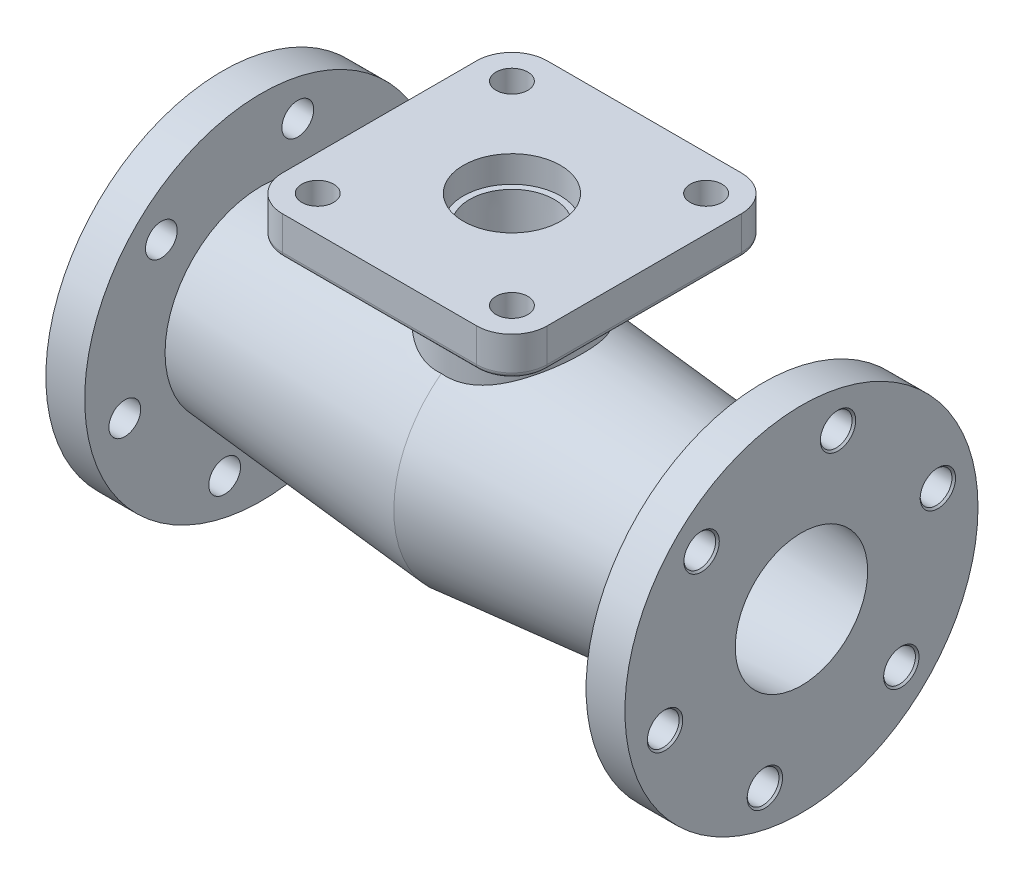
SolidWorks part; units mm, degrees
ref_plane "Front Plane" through (0, 0, 0) normal (0, 0, 1) x (1, 0, 0)
ref_plane "Top Plane" through (0, 0, 0) normal (0, 1, 0) x (1, 0, 0)
ref_plane "Right Plane" through (0, 0, 0) normal (1, 0, 0) x (0, 0, -1)
sketch "Sketch1" plane through (0, 0, 0) normal (0, 0, 1) x (1, 0, 0)
  line L0 (0, 0) -> (0, 98620.7422) construction
  line L1 (0, 0) -> (-98620.7422, 0) construction
  line L2 (0, -51.8481) -> (-164, -37.5)
  line L3 (-164, -37.5) -> (-164, -100)
  line L4 (-164, -100) -> (-142, -100)
  line L5 (-142, -100) -> (-142, -54.482)
  line L6 (-142, -54.482) -> (0, -66.9054)
  line L7 (142, -100) -> (142, -54.482)
  line L8 (164, -100) -> (142, -100)
  line L9 (164, -37.5) -> (164, -100)
  line L10 (0, -51.8481) -> (164, -37.5)
  line L11 (142, -54.482) -> (0, -66.9054)
  dimension "D1" = 284
  dimension "D2" = 328
  dimension "D3" = 5
  dimension "D4" = 200
  dimension "D5" = 75
  dimension "D6" = 15
revolve "Revolve1" add sketch "Sketch1" angle 360 about L1
ref_plane "Plane2" through (0, 122, 0) normal (0, 1, 0) x (1, 0, 0)
sketch "Sketch6" plane through (0, 122, 0) normal (0, 1, 0) x (1, 0, 0)
  line L0 (0, 66.9054) -> (0, -66.9054) construction
  line L2 (-55, 75) -> (55, 75)
  line L3 (-75, 55) -> (-75, -55)
  line L4 (-55, -75) -> (55, -75)
  line L5 (75, 55) -> (75, -55)
  line L6 (-75, 75) -> (75, -75) construction
  line L7 (-75, -75) -> (75, 75) construction
  circle A0 centre (0, 0) radius 40
  arc A1 (55, 75) -> (75, 55) centre (55, 55) cw
  arc A2 (-75, -55) -> (-55, -75) centre (-55, -55) ccw
  arc A3 (-55, 75) -> (-75, 55) centre (-55, 55) ccw
  arc A4 (55, -75) -> (75, -55) centre (55, -55) ccw
  circle A5 centre (-55, 55) radius 9
  circle A6 centre (-55, -55) radius 9
  circle A7 centre (55, -55) radius 9
  circle A8 centre (55, 55) radius 9
  dimension "D1" = 80
  dimension "D4" = 20
  dimension "D5" = 18
  dimension "D2" = 150
  dimension "D3" = 150
extrude "Boss-Extrude2" add sketch "Sketch6" against normal blind 22 separate body
extrude "Boss-Extrude3" add sketch "Sketch6<2>" against normal up to next contours A0 region at (0, 122, 0)
sketch "Sketch6<2>" plane through (0, 122, 0) normal (0, 1, 0) x (1, 0, 0) same geometry as "Sketch6"
sketch "Sketch8" plane through (0, 0, 0) normal (0, 0, 1) x (1, 0, 0)
  line L0 (0, -127.5078) -> (0, 200.2309) construction
  line L1 (0, 122) -> (0, 51.219)
  line L2 (0, 51.219) -> (23.0263, 51.219)
  line L3 (23.0263, 51.219) -> (24, 107)
  line L4 (24, 107) -> (27.5, 107)
  line L5 (27.5, 107) -> (27.5, 122)
  line L6 (27.5, 122) -> (0, 122)
  line L7 (-55, 122) -> (55, 122) construction
  dimension "D1" = 55
  dimension "D2" = 48
  dimension "D3" = 1
  dimension "D4" = 15
revolve "Cut-Revolve1" cut sketch "Sketch8" angle 360 about L0
fillet "Fillet1" radius 3 8 edges at (-69.1421, 100, -69.1421) (0, 100, -75) (69.1421, 100, -69.1421) (75, 100, 0) (69.1421, 100, 69.1421) (0, 100, 75) (-69.1421, 100, 69.1421) (-75, 100, 0)
hole_wizard "Ø20.0mm Dowel Hole2" positions "Sketch15" profile "Sketch16" hole size "Ø20.0" standard "ISO" end condition up to next
sketch "Sketch15" plane through (164, 0, 0) normal (1, 0, 0) x (0, 0, -1)
  line L0 (0, 0) -> (0, -50000) construction
  line L1 (0, 0) -> (-50000, 0) construction
  line L2 (0, 0) -> (48296.2913, 12940.9523) construction
  circle A0 centre (0, 0) radius 80 construction
  point P0 (-77.2741, -20.7055)
  dimension "D2" = 160
  dimension "D1" = 15
sketch "Sketch16" plane through (164, -20.7055, 77.2741) normal (0, 1, 0) x (0, 0, -1)
  line L0 (0, 0) -> (0, 22)
  line L1 (0, 22) -> (9, 22)
  line L2 (9, 22) -> (9, 1.025)
  line L3 (9, 1.025) -> (10.025, 0)
  line L5 (10.025, 0) -> (0, 0)
  line L6 (-9, 1.025) -> (-10.025, 0) construction
  line L11 (0, -6.35) -> (0, 107.95) construction
  dimension "Thru Hole Dia." = 18
  dimension "Thru Hole Depth" = 22
  dimension "Near C'Sink Dia." = 20.05
  dimension "Near C'Sink Angle" = 90
pattern_circular "CirPattern5" count 6 over 360 about axis through (164, 0, 0) along (1, 0, 0) of "Ø20.0mm Dowel Hole2"
mirror "Mirror1" about plane through (0, 0, 0) normal (1, 0, 0) of "CirPattern5", "Ø20.0mm Dowel Hole2"
